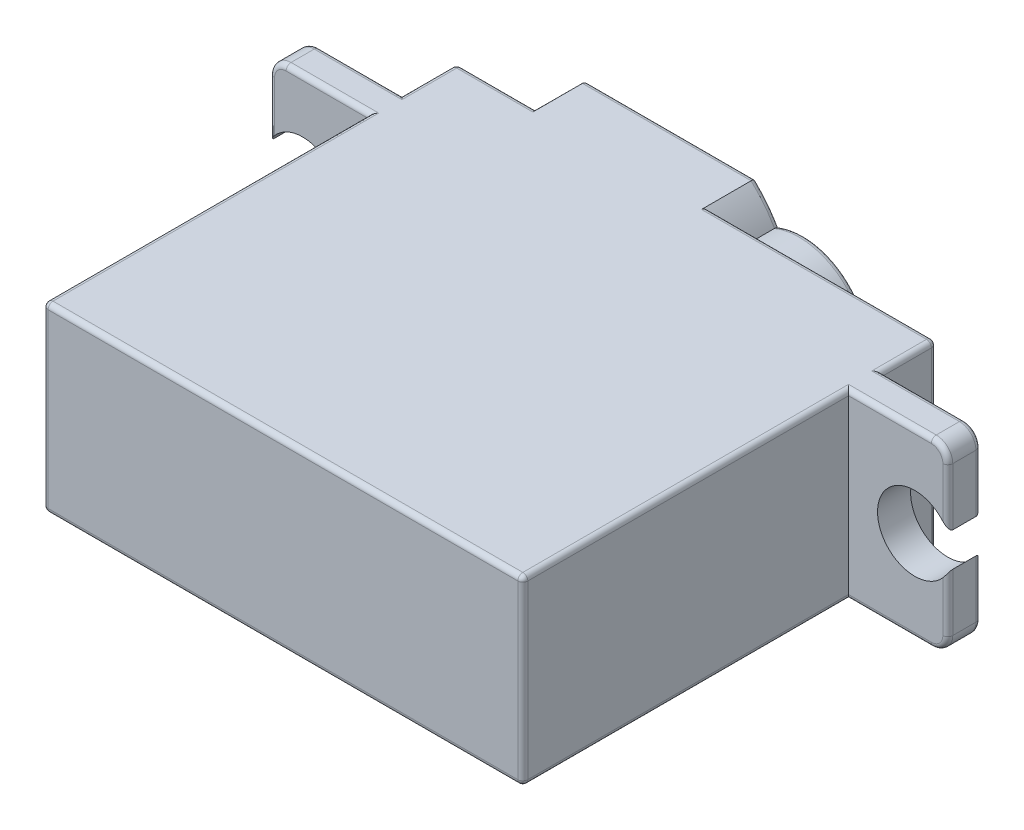
SolidWorks part; units mm, degrees
ref_plane "Front Plane" through (0, 0, 0) normal (0, 0, 1) x (1, 0, 0)
ref_plane "Top Plane" through (0, 0, 0) normal (0, 1, 0) x (1, 0, 0)
ref_plane "Right Plane" through (0, 0, 0) normal (1, 0, 0) x (0, 0, -1)
sketch "Sketch1" plane through (0, 0, 0) normal (0, 1, 0) x (1, 0, 0)
  line L0 (-14.5, 9.1905) -> (-14.5, 12.5)
  line L1 (14.5, -12.5) -> (-14.5, -12.5)
  line L2 (14.5, -12.5) -> (14.5, 7.1905)
  line L3 (14.5, 12.5) -> (-14.5, 12.5)
  line L4 (-14.5, -12.5) -> (-14.5, 7.1905)
  line L5 (14.5, -12.5) -> (-14.5, 12.5) construction
  line L6 (14.5, 12.5) -> (-14.5, -12.5) construction
  line L7 (14.5, 9.1905) -> (20.5, 9.1905)
  line L9 (14.5, 7.1905) -> (20.5, 7.1905)
  line L10 (20.5, 9.1905) -> (20.5, 7.1905)
  line L11 (-14.5, 9.1905) -> (-20.5, 9.1905)
  line L12 (14.5, 9.1905) -> (14.5, 12.5)
  line L13 (-14.5, 7.1905) -> (-20.5, 7.1905)
  line L14 (-20.5, 9.1905) -> (-20.5, 7.1905)
  point P0 (0, 0)
  dimension "D1" = 29
  dimension "D2" = 25
  dimension "D3" = 6
  dimension "D4" = 6
  dimension "D5" = 2
  dimension "D6" = 2
extrude "Boss-Extrude1" add sketch "Sketch1" along normal blind 11
sketch "Sketch2" plane through (0, 0, -12.5) normal (0, 0, -1) x (-1, 0, 0)
  line L0 (14.5, 11) -> (14.5, 0) construction
  line L1 (-14.5, 11) -> (14.5, 11) construction
  line L2 (-14.5, 0) -> (14.5, 0) construction
  line L3 (-0.599, 11) -> (9.599, 11)
  line L4 (-0.599, 0) -> (9.599, 0)
  arc A0 (9.599, 0) -> (9.599, 11) centre (4.5, 5.5) ccw
  arc A1 (-2.0156, 9.2144) -> (-2.0156, 1.7856) centre (-3.5, 5.5) ccw
  arc A2 (-0.599, 11) -> (-2.0156, 9.2144) centre (4.5, 5.5) ccw
  arc A3 (-2.0156, 1.7856) -> (-0.599, 0) centre (4.5, 5.5) ccw
  dimension "D1" = 10
  dimension "D2" = 15
  dimension "D4" = 8
  dimension "D3" = 8
extrude "Boss-Extrude2" add sketch "Sketch2" along normal blind 3
sketch "Sketch3" plane through (0, 0, -15.5) normal (0, 0, -1) x (-1, 0, 0)
  circle A0 centre (4.5, 5.5) radius 2
  dimension "D1" = 4
extrude "Boss-Extrude3" add sketch "Sketch3" along normal blind 3
fillet "Fillet2" radius 0.3 37 edges at (-14.5, 5.5, -12.5) (14.5, 5.5, -12.5) (-20.5, 5.5, -9.1905) (-4.5, 11, -15.5) (-14.5, 11, -10.8453) (-17.5, 11, -9.1905) (-14.5, 11, 2.6547) (14.5, 11, 2.6547) (20.5, 5.5, -9.1905) (17.5, 11, -9.1905) (14.5, 11, -10.8453) (1.3756, 10.1613, -15.5) (20.5, 5.5, -7.1905) (-20.5, 5.5, -7.1905) (-17.5, 11, -7.1905) (17.5, 11, -7.1905) (14.5, 5.5, 12.5) (0, 11, 12.5) (-14.5, 5.5, 12.5) (-14.5, 0, 2.6547) (-17.5, 0, -7.1905) (-14.5, 0, -10.8453) (-17.5, 0, -9.1905) (-6.5, 5.5, -18.5) (-12, 5.5, -15.5) (7.5, 5.5, -15.5) (1.3756, 0.8387, -15.5) (-4.5, 0, -15.5) (14.5, 0, -10.8453) (17.5, 0, -9.1905) (17.5, 0, -7.1905) (14.5, 0, 2.6547) (0, 0, 12.5)
fillet "Fillet3" radius 1 12 edges at (-20.4121, 0.0879, -7.2784) (-20.4121, 0.0879, -9.1027) (-20.4121, 10.9121, -7.2784) (-20.4121, 10.9121, -9.1027) (20.4121, 10.9121, -9.1027) (20.4121, 10.9121, -7.2784) (20.4121, 0.0879, -9.1027) (20.4121, 0.0879, -7.2784) (20.5, 0, -8.1905) (20.5, 11, -8.1905) (-20.5, 11, -8.1905) (-20.5, 0, -8.1905)
sketch "Sketch4" plane through (0, 0, -9.1905) normal (0, 0, -1) x (-1, 0, 0)
  line L0 (-20.5, 1) -> (-20.5, 10) construction
  line L1 (-19.5, 0) -> (-14.2, 0) construction
  circle A0 centre (-18.5, 5.5) radius 2.25
  dimension "D1" = 4.5
  dimension "D2" = 2
extrude "Cut-Extrude1" cut sketch "Sketch4" against normal through all
mirror "Mirror1" about plane through (0, 0, 0) normal (1, 0, 0) of "Cut-Extrude1"
